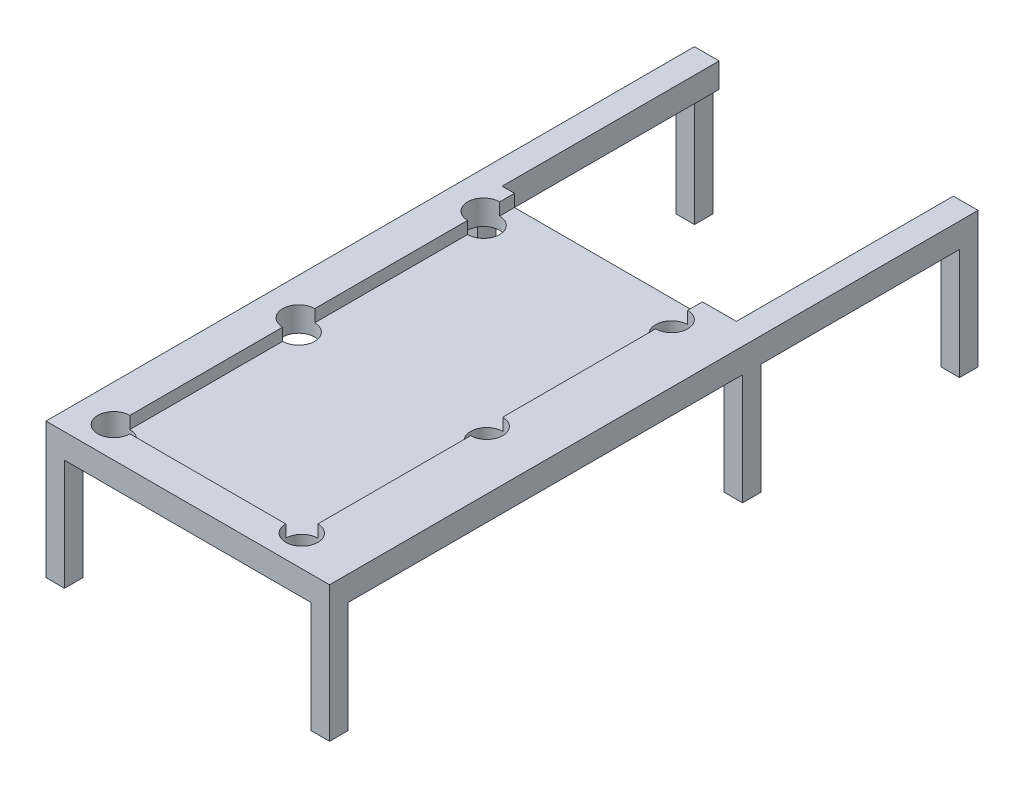
SolidWorks part; units mm, degrees
ref_plane "Front Plane" through (0, 0, 0) normal (0, 0, 1) x (1, 0, 0)
ref_plane "Top Plane" through (0, 0, 0) normal (0, 1, 0) x (1, 0, 0)
ref_plane "Right Plane" through (0, 0, 0) normal (1, 0, 0) x (0, 0, -1)
sketch "Sketch2" plane through (0, 0, 0) normal (0, 1, 0) x (1, 0, 0)
  line L1 (0, 0) -> (460, 0)
  line L2 (0, 0) -> (0, 700)
  line L3 (0, 700) -> (460, 700)
  line L4 (460, 0) -> (460, 700)
  line L5 (60, 50) -> (365, 50)
  line L6 (60, 50) -> (60, 650)
  line L7 (60, 650) -> (365, 650)
  line L8 (365, 50) -> (365, 650)
  dimension "D1" = 700
  dimension "D2" = 460
  dimension "D3" = 600
  dimension "D4" = 305
  dimension "D5" = 60
  dimension "D6" = 50
extrude "Boss-Extrude1" add sketch "Sketch2" along normal blind 20
ref_plane "Plane1" through (0, 0, -700) normal (0, 0, -1) x (-1, 0, 0)
sketch "Sketch10" plane through (0, 0, 0) normal (0, -1, 0) x (1, 0, 0)
  line L1 (0, 0) -> (460, 0)
  line L2 (0, 0) -> (0, -700)
  line L3 (0, -700) -> (460, -700)
  line L4 (460, 0) -> (460, -700)
extrude "Boss-Extrude6" add sketch "Sketch10" along normal blind 20
sketch "Sketch11" plane through (0, -20, 0) normal (0, -1, 0) x (1, 0, 0)
  line L1 (0, 0) -> (30, 0)
  line L2 (0, 0) -> (0, -30)
  line L3 (0, -30) -> (30, -30)
  line L4 (30, 0) -> (30, -30)
  line L5 (460, 0) -> (430, 0)
  line L6 (460, 0) -> (460, -30)
  line L7 (460, -30) -> (430, -30)
  line L8 (430, 0) -> (430, -30)
  line L9 (0, -700) -> (30, -700)
  line L10 (0, -700) -> (0, -670)
  line L11 (0, -670) -> (30, -670)
  line L12 (30, -700) -> (30, -670)
  line L13 (460, -700) -> (430, -700)
  line L14 (460, -700) -> (460, -670)
  line L15 (460, -670) -> (430, -670)
  line L16 (430, -700) -> (430, -670)
  dimension "D1" = 30
extrude "Boss-Extrude7" add sketch "Sketch11" along normal blind 180
sketch "Sketch14" plane through (0, 20, 0) normal (0, 1, 0) x (1, 0, 0)
  line L0 (22, 700) -> (-22, 700) construction
  line L1 (0, 700) -> (40, 700)
  line L2 (0, 700) -> (0, 1052)
  line L3 (0, 1052) -> (40, 1052)
  line L4 (40, 700) -> (40, 1052)
  line L5 (0, 700) -> (0, 0) construction
  line L6 (460, 0) -> (460, 700) construction
  line L7 (460, 700) -> (420, 700)
  line L8 (460, 700) -> (460, 1052)
  line L9 (460, 1052) -> (420, 1052)
  line L10 (420, 700) -> (420, 1052)
  line L11 (330, 1052) -> (390, 1052) construction
  dimension "D3" = 40
  dimension "D4" = 40
extrude "Boss-Extrude8" add sketch "Sketch14" against normal blind 40
sketch "Sketch15" plane through (0, -20, 0) normal (0, -1, 0) x (1, 0, 0)
  line L1 (460, -1052) -> (430, -1052)
  line L2 (460, -1052) -> (460, -1022)
  line L3 (460, -1022) -> (430, -1022)
  line L4 (430, -1052) -> (430, -1022)
  line L6 (0, -1052) -> (30, -1052)
  line L7 (0, -1052) -> (0, -1022)
  line L8 (0, -1022) -> (30, -1022)
  line L9 (30, -1052) -> (30, -1022)
  dimension "D1" = 30
  dimension "D2" = 30
  dimension "D3" = 30
  dimension "D4" = 30
extrude "Boss-Extrude9" add sketch "Sketch15" along normal blind 180
sketch "Sketch17" plane through (0, 20, 0) normal (0, 1, 0) x (1, 0, 0)
  line L0 (60, 650) -> (60, 50) construction
  line L1 (365, 50) -> (365, 650) construction
  circle A0 centre (60, 650) radius 26
  circle A1 centre (60, 350) radius 26
  circle A2 centre (60, 50) radius 26
  circle A3 centre (365, 50) radius 26
  circle A4 centre (365, 350) radius 26
  circle A5 centre (365, 650) radius 26
  line M15 (60, 50) -> (60, 650)
  line M16 (60, 650) -> (365, 650)
  line M17 (365, 650) -> (365, 50)
  line M18 (365, 50) -> (60, 50)
  dimension "D1" = 52
extrude "Cut-Extrude1" cut sketch "Sketch17" against normal blind 60 contours A5 M17 M16 | A4 M17 | A3 M18 M17 | A1 M15 | A1 M15 | A2 M15 M18 | A2 M18 M15 | A3 M17 M18 | A5 M16 M17 | A4 M17 | A0 region at (353.9653, 20, -638.9653) region at (368.6782, 20, -653.6782) region at (48.9653, 20, -350) region at (71.0347, 20, -350) region at (353.9653, 20, -350) region at (376.0347, 20, -350) region at (56.3218, 20, -46.3218) region at (71.0347, 20, -61.0347) region at (353.9653, 20, -61.0347) region at (368.6782, 20, -46.3218)
sketch "Sketch18" plane through (0, 20, 0) normal (0, 1, 0) x (1, 0, 0)
  line L1 (60, 700) -> (365, 700)
  line L9 (339, 650) -> (86, 650) construction
  line L10 (420, 700) -> (40, 700) construction
  line L12 (365, 700) -> (365, 650)
  line L14 (212.5, 650) -> (365, 650)
  line L16 (60, 700) -> (60, 650)
  line L17 (60, 650) -> (212.5, 650)
  arc A0 (86, 650) -> (60, 624) centre (60, 650) ccw construction
  arc A1 (365, 624) -> (339, 650) centre (365, 650) ccw construction
extrude "Cut-Extrude2" cut sketch "Sketch18" against normal blind 20
